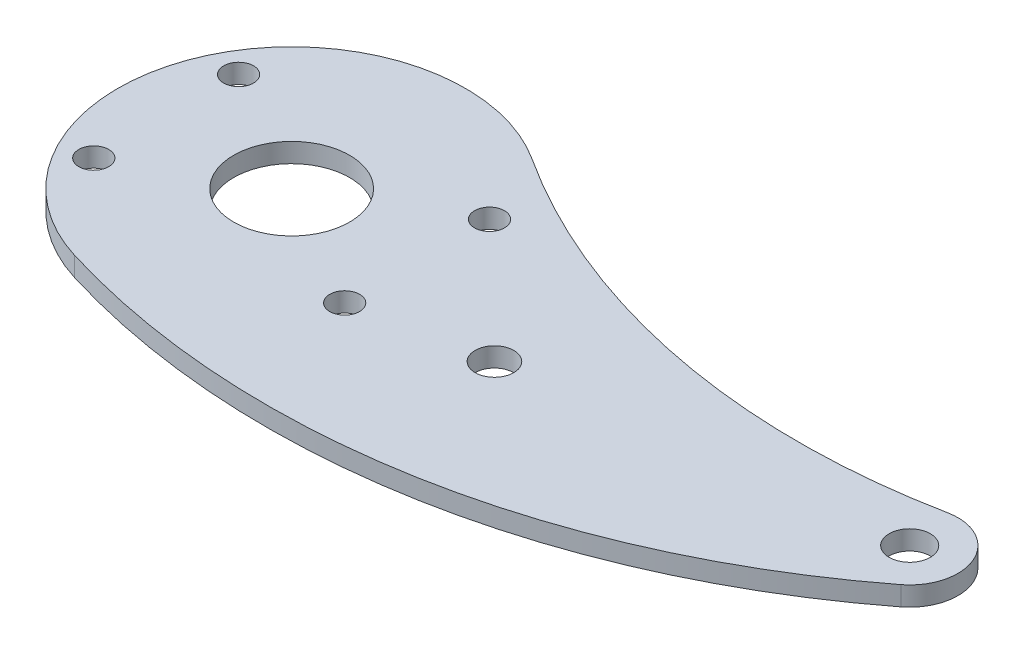
SolidWorks part; units mm, degrees
material "6061-T6 (SS)"
ref_plane "Front" through (0, 0, 0) normal (0, 0, 1) x (1, 0, 0)
ref_plane "Top" through (0, 0, 0) normal (0, 1, 0) x (1, 0, 0)
ref_plane "Right" through (0, 0, 0) normal (1, 0, 0) x (0, 0, -1)
sketch "Sketch1" plane through (0, 0, 0) normal (0, 1, 0) x (1, 0, 0)
  arc A0 (15.5451, 23.9767) -> (-8.3356, -27.3322) centre (0, 0) ccw
  circle A1 centre (0, 0) radius 9.525
  arc A2 (106.4592, -6.2763) -> (100.0497, 7.7846) centre (101.6, 0) ccw
  circle A3 centre (101.6, 0) radius 3.3782
  arc A5 (15.5451, 23.9767) -> (100.0497, 7.7846) centre (77.7255, 119.8833) ccw
  arc A6 (-8.3356, -27.3322) -> (106.4592, -6.2763) centre (28.7114, 94.1442) ccw
  dimension "D2" = 57.15
  dimension "D3" = 15.875
  dimension "D4" = 6.7564
  dimension "D1" = 19.05
  dimension "D6" = 114.3
  dimension "D7" = 127
  dimension "D5" = 101.6
extrude "Boss-Extrude1" add sketch "Sketch1" along normal blind 3.175 contours A2 A0 | A0 | A2 A3 region at (31.3101, 0, 5.5999)
sketch "Sketch4" plane through (0, 3.175, 0) normal (0, 1, 0) x (1, 0, 0)
  circle A0 centre (0, 0) radius 23.8125
  point P7 (-20.6222, 11.9062)
  point P9 (20.6222, 11.9062)
  point P11 (20.6222, -11.9062)
  point P13 (-20.6222, -11.9062)
  dimension "D1" = 47.625
  dimension "D2" = 23.8125
hole_wizard "#10 (0.1935) Diameter Hole1" positions "Sketch4" profile "Sketch3" hole size "#10" standard "ANSI Inch" end condition through all
sketch "Sketch3" plane through (-20.6222, 3.175, 11.9062) normal (1, 0, 0) x (0, 0, 1)
  line L0 (0, 0) -> (0, 3.175)
  line L1 (0, 3.175) -> (2.4574, 3.175)
  line L2 (2.4574, 3.175) -> (2.4574, 0)
  line L5 (2.4574, 0) -> (0, 0)
  line L11 (0, -6.35) -> (0, 107.95) construction
  dimension "Thru Hole Dia." = 4.9149
  dimension "Thru Hole Depth" = 3.175
sketch "Sketch7" plane through (0, 3.175, 0) normal (0, 1, 0) x (1, 0, 0)
  line L3 (41.275, -7.9375) -> (101.6, 0) construction
  line L6 (0, 0) -> (101.6, 0) construction
  circle A0 centre (101.6, 0) radius 3.3782 construction
  point P0 (41.275, -7.9375)
  dimension "D1" = 7.9375
  dimension "D2" = 60.325
hole_wizard "1/4 (0.25) Diameter Hole2" positions "Sketch7" profile "Sketch8" hole size "1/4" standard "ANSI Inch" end condition through all
sketch "Sketch8" plane through (41.275, 3.175, 7.9375) normal (1, 0, 0) x (0, 0, 1)
  line L0 (0, 0) -> (0, 3.175)
  line L1 (0, 3.175) -> (3.175, 3.175)
  line L2 (3.175, 3.175) -> (3.175, 0)
  line L5 (3.175, 0) -> (0, 0)
  line L11 (0, -6.35) -> (0, 107.95) construction
  dimension "Thru Hole Dia." = 6.35
  dimension "Thru Hole Depth" = 3.175
